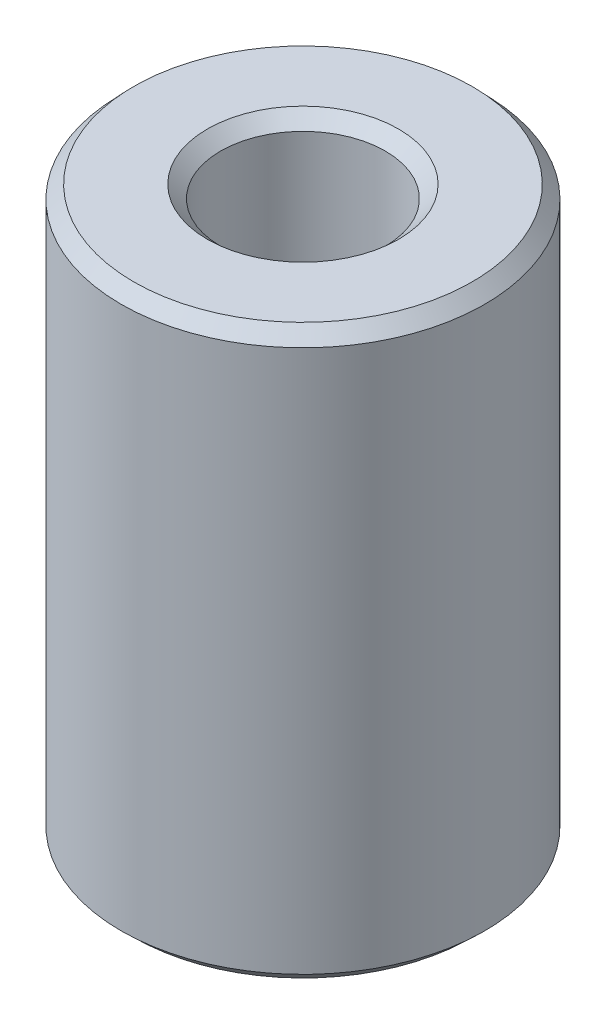
SolidWorks part; units mm, degrees
ref_plane "Front Plane" through (0, 0, 0) normal (0, 0, 1) x (1, 0, 0)
ref_plane "Top Plane" through (0, 0, 0) normal (0, 1, 0) x (1, 0, 0)
ref_plane "Right Plane" through (0, 0, 0) normal (1, 0, 0) x (0, 0, -1)
sketch "Sketch1" plane through (0, 0, 0) normal (0, 1, 0) x (1, 0, 0)
  circle A0 centre (0, 0) radius 42.5
  dimension "SLEEVE_OD" = 85
extrude "Boss-Extrude1" add sketch "Sketch1" along normal blind 132.9019
sketch "Sketch2" plane through (0, 0, 0) normal (0, 1, 0) x (1, 0, 0)
  circle A0 centre (0, 0) radius 19.2651
  dimension "BORE_D" = 38.5302
extrude "Cut-Extrude1" cut sketch "Sketch2" along normal through all
chamfer "Chamfer1" distance 3.0897 angle 43.397 4 edges at (0, 132.9019, 19.2651) (0, 0, 19.2651) (0, 0, 42.5) (0, 132.9019, 42.5) first distance on face at (0, 132.9019, 19.2651) first distance on face at (0, 0, 19.2651) first distance on face at (0, 132.9019, 42.5)
